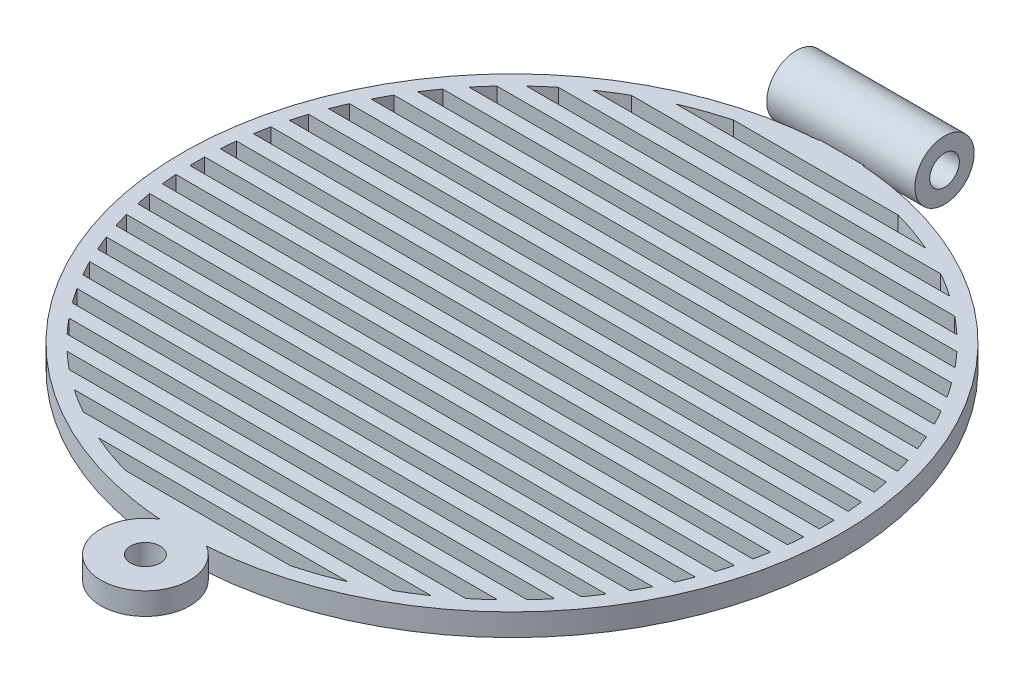
SolidWorks part; units mm, degrees
ref_plane "Front Plane" through (0, 0, 0) normal (0, 0, 1) x (1, 0, 0)
ref_plane "Top Plane" through (0, 0, 0) normal (0, 1, 0) x (1, 0, 0)
ref_plane "Right Plane" through (0, 0, 0) normal (1, 0, 0) x (0, 0, -1)
sketch "Sketch1" plane through (0, 0, 0) normal (0, 1, 0) x (1, 0, 0)
  line L1 (-1.5, 24.1894) -> (1.5, 24.1894)
  line L2 (-1.5, 24.1894) -> (-1.5, 22.1894)
  line L3 (-1.5, 22.1894) -> (1.5, 22.1894)
  line L4 (1.5, 24.1894) -> (1.5, 22.1894)
  line L5 (-1.5, 24.1894) -> (1.5, 22.1894) construction
  line L6 (-1.5, 22.1894) -> (1.5, 24.1894) construction
  circle A2 centre (0, -24.74) radius 3
  circle A3 centre (0, -24.74) radius 1
  ellipse E0 centre (0, 0) end of major axis (-21.24, 0) minor radius 21.24
  ellipse E1 centre (0, 0) end of major axis (-22.24, 0) minor radius 22.24
  point P7 (0, 23.1894)
  dimension "D1" = 1
  dimension "D2" = 21.24
  dimension "D3" = 2
  dimension "D4" = 2
  dimension "D5" = 2.5
  dimension "D6" = 3
  dimension "D7" = 0
  dimension "D8" = 2
  dimension "D9" = 21.24
  dimension "D10" = 1
  dimension "D11" = 0
extrude "Boss-Extrude1" add sketch "Sketch1" along normal blind 1.5 contours E1 A2 A3 | E1 A2 | A2 E1 L3 | L3 E1 | E1 L4 L1 L2 region at (0, 0, -23.2062) region at (0, 0, -22.2096) region at (0, 0, -21.5611) region at (0, 0, 22.0275) region at (2.5472, 0, 23.316)
sketch "Sketch2" plane through (0, 0, 0) normal (1, 0, 0) x (0, 0, -1)
  line L0 (-22.1844, 0) -> (22.1894, 0) construction
  line L2 (24.1894, 1.5) -> (24.1894, 0) construction
  circle A0 centre (24.1894, 2) radius 1
  circle A1 centre (24.1894, 2) radius 2
  dimension "D1" = 2
  dimension "D2" = 1
  dimension "D3" = 0
  dimension "2.5" = 2
extrude "Boss-Extrude2" add sketch "Sketch2" along normal blind 5 and the other way blind 5
sketch "Sketch4" plane through (5, 0, 0) normal (1, 0, 0) x (0, 0, -1)
  circle A0 centre (24.1894, 2) radius 1
extrude "Cut-Extrude1" cut sketch "Sketch4" against normal through all
sketch "Sketch5" plane through (0, 1.5, 0) normal (0, 1, 0) x (1, 0, 0)
  line L0 (-21.2341, -0.5) -> (21.2341, -0.5)
  line L1 (21.2341, 0.5) -> (-21.2341, 0.5)
  line L2 (21.2341, 2.5) -> (-21.2341, 2.5)
  line L3 (-21.2341, 1.5) -> (21.2341, 1.5)
  line L4 (21.2341, 4.5) -> (-21.2341, 4.5)
  line L5 (-21.2341, 3.5) -> (21.2341, 3.5)
  line L6 (21.2341, 6.5) -> (-21.2341, 6.5)
  line L7 (-21.2341, 5.5) -> (21.2341, 5.5)
  line L8 (21.2341, 8.5) -> (-21.2341, 8.5)
  line L9 (-21.2341, 7.5) -> (21.2341, 7.5)
  line L10 (21.2341, 10.5) -> (-21.2341, 10.5)
  line L11 (-21.2341, 9.5) -> (21.2341, 9.5)
  line L12 (21.2341, 12.5) -> (-21.2341, 12.5)
  line L13 (-21.2341, 11.5) -> (21.2341, 11.5)
  line L14 (21.2341, 14.5) -> (-21.2341, 14.5)
  line L15 (-21.2341, 13.5) -> (21.2341, 13.5)
  line L16 (21.2341, 16.5) -> (-21.2341, 16.5)
  line L17 (-21.2341, 15.5) -> (21.2341, 15.5)
  line L18 (21.2341, 18.5) -> (-21.2341, 18.5)
  line L19 (-21.2341, 17.5) -> (21.2341, 17.5)
  line L20 (21.2341, 20.5) -> (-21.2341, 20.5)
  line L21 (-21.2341, 19.5) -> (21.2341, 19.5)
  line L22 (21.2341, -1.5) -> (-21.2341, -1.5)
  line L23 (-21.2341, -2.5) -> (21.2341, -2.5)
  line L24 (21.2341, -3.5) -> (-21.2341, -3.5)
  line L25 (-21.2341, -4.5) -> (21.2341, -4.5)
  line L26 (21.2341, -5.5) -> (-21.2341, -5.5)
  line L27 (-21.2341, -6.5) -> (21.2341, -6.5)
  line L28 (21.2341, -7.5) -> (-21.2341, -7.5)
  line L29 (-21.2341, -8.5) -> (21.2341, -8.5)
  line L30 (21.2341, -9.5) -> (-21.2341, -9.5)
  line L31 (-21.2341, -10.5) -> (21.2341, -10.5)
  line L32 (21.2341, -11.5) -> (-21.2341, -11.5)
  line L33 (-21.2341, -12.5) -> (21.2341, -12.5)
  line L34 (21.2341, -13.5) -> (-21.2341, -13.5)
  line L35 (-21.2341, -14.5) -> (21.2341, -14.5)
  line L36 (21.2341, -15.5) -> (-21.2341, -15.5)
  line L37 (-21.2341, -16.5) -> (21.2341, -16.5)
  line L38 (21.2341, -17.5) -> (-21.2341, -17.5)
  line L39 (-21.2341, -18.5) -> (21.2341, -18.5)
  line L40 (21.2341, -19.5) -> (-21.2341, -19.5)
  line L41 (-21.2341, -20.5) -> (21.2341, -20.5)
  circle A0 centre (0, 0) radius 21.24 construction
  ellipse E0 centre (0, 0) end of major axis (21.24, 0) minor radius 21.24
  ellipse M10 centre (0, 0) end of major axis (0, -21.24) minor radius 21.24
  dimension "D1" = 0.5
  dimension "D2" = 0.5
  dimension "D3" = 11
  dimension "D4" = 11
extrude "Boss-Extrude3" add sketch "Sketch5" against normal up to surface (1.5 mm away) contours L22 L0 M10 | L3 L1 M10 | L5 L2 M10 | L7 L4 M10 | L9 L6 M10 | L24 L23 M10 | L26 L25 M10 | L28 L27 M10 | L30 L29 M10 | L32 L31 M10 | L34 L33 M10 | L36 L35 M10 | L38 L37 M10 | L40 L39 M10 | L41 M10 | L11 L8 M10 | L13 L10 M10 | L15 L12 M10 | L17 L14 M10 | L19 L16 M10 | L21 L18 M10 | L20 M10 region at (0, 1.5, 0.9998) region at (0, 1.5, -0.9998) region at (0, 1.5, 2.9994) region at (0, 1.5, -2.9994) region at (0, 1.5, 4.999) region at (0, 1.5, -4.999) region at (0, 1.5, 6.9985) region at (0, 1.5, -6.9985) region at (0, 1.5, 8.998) region at (0, 1.5, -8.998) region at (0, 1.5, 10.9972) region at (0, 1.5, -10.9972) region at (0, 1.5, 12.9962) region at (0, 1.5, -12.9962) region at (0, 1.5, 14.9945) region at (0, 1.5, -14.9945) region at (0, 1.5, 16.9912) region at (0, 1.5, -16.9912) region at (0, 1.5, 18.9823) region at (0, 1.5, -18.9823) region at (0, 1.5, 20.7964) region at (0, 1.5, -20.7964) up to face at (0, 0, -7.1499)
sketch "Sketch6" plane through (0, 0, 0) normal (0, -1, 0) x (1, 0, 0)
  line L0 (-0.1, 19.5) -> (-0.1, 17.0155)
  line L1 (9.9, 17.0155) -> (10.1, 17.0155)
  line L2 (7.9, -8.5) -> (7.9, -10.5)
  line L3 (0.1, 19.5) -> (0.1, 17.0155)
  line L4 (1.9, 20.5) -> (1.9, 19.5)
  line L5 (2.1, 20.5) -> (2.1, 19.5)
  line L6 (3.9, 19.5) -> (3.9, 17.0155)
  line L7 (4.1, 19.5) -> (4.1, 17.0155)
  line L8 (5.9, 20.5) -> (5.9, 19.5)
  line L9 (6.1, 20.5) -> (6.1, 19.5)
  line L10 (7.9, 19.5) -> (7.9, 17.0155)
  line L11 (8.1, 19.5) -> (8.1, 17.0155)
  line L12 (9.9, 17.0155) -> (9.9, 15.0879)
  line L13 (10.1, 17.0155) -> (10.1, 15.0879)
  line L14 (11.9, 15.0879) -> (11.9, 13.5)
  line L15 (12.1, 15.0879) -> (12.1, 13.5)
  line L16 (13.9, 17.0155) -> (13.9, 15.0879)
  line L17 (14.1, 17.0155) -> (14.1, 15.0879)
  line L18 (15.9, 15.0879) -> (15.9, 13.5)
  line L19 (16.1, 15.0879) -> (16.1, 13.5)
  line L20 (8.1, 15.0879) -> (8.1, 13.5)
  line L21 (7.9, 15.0879) -> (7.9, 13.5)
  line L24 (-1.9, 20.5) -> (-1.9, 19.5)
  line L25 (-2.1, 20.5) -> (-2.1, 19.5)
  line L26 (-3.9, 19.5) -> (-3.9, 17.0155)
  line L27 (-4.1, 19.5) -> (-4.1, 17.0155)
  line L28 (-5.9, 20.5) -> (-5.9, 19.5)
  line L29 (-6.1, 20.5) -> (-6.1, 19.5)
  line L30 (-7.9, 19.5) -> (-7.9, 16.8952)
  line L31 (-8.1, 19.5) -> (-8.1, 16.8952)
  line L32 (-9.9, 16.8952) -> (-9.9, 15.0134)
  line L33 (-10.1, 16.8952) -> (-10.1, 15.0134)
  line L34 (-11.9, 15.0134) -> (-11.9, 13.5)
  line L35 (-12.1, 15.0134) -> (-12.1, 13.5)
  line L36 (-13.9, 16.8952) -> (-13.9, 15.0134)
  line L37 (-14.1, 16.8952) -> (-14.1, 15.0134)
  line L38 (-16.1, 15.0134) -> (-15.9, 15.0134)
  line L39 (-8.1, 19.5) -> (-7.9, 19.5)
  line L40 (-17.9, 9.5) -> (-17.9, 7.5)
  line L41 (-18.1, 9.5) -> (-18.1, 7.5)
  line L42 (-19.9, 7.5) -> (-19.9, 5.5)
  line L43 (-20.1, 7.5) -> (-20.1, 5.5)
  line L44 (-20.1, -0.5) -> (-19.9, -0.5)
  line L45 (-20.1, 1.5) -> (-19.9, 1.5)
  line L46 (-20.1, 3.5) -> (-19.9, 3.5)
  line L47 (-20.1, 5.5) -> (-19.9, 5.5)
  line L48 (-20.1, 7.5) -> (-19.9, 7.5)
  line L49 (-18.1, 9.5) -> (-17.9, 9.5)
  line L50 (-14.1, 9.5) -> (-13.9, 9.5)
  line L51 (-18.1, 1.5) -> (-18.1, -0.5)
  line L52 (-7.9, 15.0134) -> (-7.9, 13.5)
  line L53 (-8.1, 15.0134) -> (-8.1, 13.5)
  line L54 (-8.1, 15.0134) -> (-7.9, 15.0134)
  line L55 (-20.1, -2.5) -> (-19.9, -2.5)
  line L56 (-20.1, -4.5) -> (-19.9, -4.5)
  line L57 (-20.1, -6.5) -> (-19.9, -6.5)
  line L58 (-18.1, -12.5) -> (-17.9, -12.5)
  line L59 (-18.1, -10.5) -> (-17.9, -10.5)
  line L60 (3.9, -8.5) -> (3.9, -10.5)
  line L61 (4.1, -8.5) -> (4.1, -10.5)
  line L62 (5.9, -8.5) -> (6.1, -8.5)
  line L64 (-12.1, -18.5) -> (-11.9, -18.5)
  line L65 (-8.1, 13.5) -> (-7.9, 13.5)
  line L66 (-0.1, 3.5) -> (0.1, 3.5)
  line L67 (-0.1, 3.5) -> (-0.1, 1.5)
  line L68 (0.1, 3.5) -> (0.1, 1.5)
  line L69 (1.9, 3.5) -> (2.1, 3.5)
  line L70 (1.9, 1.5) -> (2.1, 1.5)
  line L71 (0.1, -0.5) -> (0.1, -2.5)
  line L72 (-0.1, -0.5) -> (-0.1, -2.5)
  line L73 (-0.1, 1.5) -> (0.1, 1.5)
  line L74 (-1.9, 1.5) -> (-1.9, -0.5)
  line L75 (-2.1, 1.5) -> (-2.1, -0.5)
  line L76 (-2.1, 3.5) -> (-1.9, 3.5)
  line L77 (-2.1, 5.5) -> (-1.9, 5.5)
  line L78 (-2.1, 5.5) -> (-2.1, 3.5)
  line L79 (-1.9, 5.5) -> (-1.9, 3.5)
  line L80 (-0.1, 5.5) -> (0.1, 5.5)
  line L81 (1.9, 5.5) -> (2.1, 5.5)
  line L82 (1.9, 5.5) -> (1.9, 3.5)
  line L83 (2.1, 5.5) -> (2.1, 3.5)
  line L84 (3.9, 5.5) -> (4.1, 5.5)
  line L85 (3.9, 3.5) -> (4.1, 3.5)
  line L86 (2.1, 1.5) -> (2.1, -0.5)
  line L87 (1.9, 1.5) -> (1.9, -0.5)
  line L88 (1.9, 7.5) -> (2.1, 7.5)
  line L89 (0.1, 7.5) -> (0.1, 5.5)
  line L90 (-0.1, 7.5) -> (-0.1, 5.5)
  line L91 (-0.1, 7.5) -> (0.1, 7.5)
  line L92 (-2.1, 7.5) -> (-1.9, 7.5)
  line L93 (-2.1, 9.5) -> (-1.9, 9.5)
  line L94 (-2.1, 9.5) -> (-2.1, 7.5)
  line L95 (-1.9, 9.5) -> (-1.9, 7.5)
  line L96 (-0.1, 9.5) -> (0.1, 9.5)
  line L97 (1.9, 9.5) -> (2.1, 9.5)
  line L98 (1.9, 9.5) -> (1.9, 7.5)
  line L99 (2.1, 9.5) -> (2.1, 7.5)
  line L100 (3.9, 9.5) -> (4.1, 9.5)
  line L101 (3.9, 7.5) -> (4.1, 7.5)
  line L102 (3.9, 1.5) -> (4.1, 1.5)
  line L103 (3.9, -0.5) -> (4.1, -0.5)
  line L104 (2.1, -2.5) -> (2.1, -4.5)
  line L105 (1.9, -2.5) -> (1.9, -4.5)
  line L106 (1.9, -0.5) -> (2.1, -0.5)
  line L107 (1.9, -2.5) -> (2.1, -2.5)
  line L108 (0.1, -4.5) -> (0.1, -6.5)
  line L109 (-0.1, -4.5) -> (-0.1, -6.5)
  line L110 (-0.1, -2.5) -> (0.1, -2.5)
  line L111 (-1.9, -2.5) -> (-1.9, -4.5)
  line L112 (-2.1, -2.5) -> (-2.1, -4.5)
  line L113 (-2.1, -0.5) -> (-1.9, -0.5)
  line L114 (-2.1, 1.5) -> (-1.9, 1.5)
  line L115 (-3.9, -0.5) -> (-3.9, -2.5)
  line L116 (-4.1, -0.5) -> (-4.1, -2.5)
  line L117 (-4.1, 1.5) -> (-3.9, 1.5)
  line L118 (-4.1, 3.5) -> (-3.9, 3.5)
  line L119 (-4.1, 3.5) -> (-4.1, 1.5)
  line L120 (-3.9, 3.5) -> (-3.9, 1.5)
  line L121 (-5.9, 1.5) -> (-5.9, -0.5)
  line L122 (-6.1, 1.5) -> (-6.1, -0.5)
  line L123 (-6.1, 3.5) -> (-5.9, 3.5)
  line L124 (-6.1, 5.5) -> (-5.9, 5.5)
  line L125 (-6.1, 5.5) -> (-6.1, 3.5)
  line L126 (-5.9, 5.5) -> (-5.9, 3.5)
  line L127 (-4.1, 5.5) -> (-3.9, 5.5)
  line L128 (-3.9, 7.5) -> (-3.9, 5.5)
  line L129 (-4.1, 7.5) -> (-4.1, 5.5)
  line L130 (-4.1, 7.5) -> (-3.9, 7.5)
  line L131 (-6.1, 7.5) -> (-5.9, 7.5)
  line L132 (-6.1, 9.5) -> (-5.9, 9.5)
  line L133 (-6.1, 9.5) -> (-6.1, 7.5)
  line L134 (-5.9, 9.5) -> (-5.9, 7.5)
  line L135 (-4.1, 9.5) -> (-3.9, 9.5)
  line L136 (-2.1, 11.5) -> (-1.9, 11.5)
  line L137 (-3.9, 11.5) -> (-3.9, 9.5)
  line L138 (-4.1, 11.5) -> (-4.1, 9.5)
  line L139 (-4.1, 11.5) -> (-3.9, 11.5)
  line L140 (-6.1, 11.5) -> (-5.9, 11.5)
  line L141 (-6.1, 13.5) -> (-5.9, 13.5)
  line L142 (-6.1, 13.5) -> (-6.1, 11.5)
  line L143 (-5.9, 13.5) -> (-5.9, 11.5)
  line L144 (-4.1, 15.0879) -> (-3.9, 15.0879)
  line L145 (-4.1, 15.0879) -> (-4.1, 13.5)
  line L146 (-3.9, 15.0879) -> (-3.9, 13.5)
  line L147 (-2.1, 15.0879) -> (-1.9, 15.0879)
  line L148 (-2.1, 13.5) -> (-1.9, 13.5)
  line L149 (-4.1, 13.5) -> (-3.9, 13.5)
  line L150 (-4.1, 17.0155) -> (-3.9, 17.0155)
  line L151 (-4.1, 19.5) -> (-3.9, 19.5)
  line L152 (-2.1, 19.5) -> (-1.9, 19.5)
  line L153 (-2.1, 17.0155) -> (-1.9, 17.0155)
  line L154 (-6.1, 15.5) -> (-5.9, 15.5)
  line L155 (-6.1, 17.5) -> (-5.9, 17.5)
  line L156 (-6.1, 17.5) -> (-6.1, 15.5)
  line L157 (-5.9, 17.5) -> (-5.9, 15.5)
  line L158 (-6.1, 19.5) -> (-5.9, 19.5)
  line L159 (-6.1, 20.5) -> (-5.9, 20.5)
  line L160 (-2.1, 20.5) -> (-1.9, 20.5)
  line L161 (-2.1, 17.0155) -> (-2.1, 15.0879)
  line L162 (-1.9, 17.0155) -> (-1.9, 15.0879)
  line L163 (-0.1, 17.0155) -> (0.1, 17.0155)
  line L164 (-0.1, 15.0879) -> (0.1, 15.0879)
  line L165 (-1.9, 13.5) -> (-1.9, 11.5)
  line L166 (-2.1, 13.5) -> (-2.1, 11.5)
  line L167 (-0.1, 11.5) -> (0.1, 11.5)
  line L168 (-0.1, 13.5) -> (0.1, 13.5)
  line L169 (-0.1, 11.5) -> (-0.1, 9.5)
  line L170 (0.1, 11.5) -> (0.1, 9.5)
  line L171 (1.9, 11.5) -> (2.1, 11.5)
  line L172 (3.9, 11.5) -> (4.1, 11.5)
  line L173 (3.9, 13.5) -> (4.1, 13.5)
  line L174 (2.1, 13.5) -> (2.1, 11.5)
  line L175 (1.9, 13.5) -> (1.9, 11.5)
  line L176 (1.9, 15.0879) -> (2.1, 15.0879)
  line L177 (1.9, 13.5) -> (2.1, 13.5)
  line L178 (0.1, 15.0879) -> (0.1, 13.5)
  line L179 (-0.1, 15.0879) -> (-0.1, 13.5)
  line L180 (-0.1, 19.5) -> (0.1, 19.5)
  line L181 (1.9, 19.5) -> (2.1, 19.5)
  line L182 (1.9, 20.5) -> (2.1, 20.5)
  line L183 (1.9, 17.0155) -> (2.1, 17.0155)
  line L184 (3.9, 15.0879) -> (4.1, 15.0879)
  line L185 (3.9, 17.0155) -> (4.1, 17.0155)
  line L186 (2.1, 17.0155) -> (2.1, 15.0879)
  line L187 (1.9, 17.0155) -> (1.9, 15.0879)
  line L188 (3.9, 19.5) -> (4.1, 19.5)
  line L189 (5.9, 20.5) -> (6.1, 20.5)
  line L190 (5.9, 19.5) -> (6.1, 19.5)
  line L191 (5.9, 17.0155) -> (6.1, 17.0155)
  line L192 (4.1, 15.0879) -> (4.1, 13.5)
  line L193 (3.9, 15.0879) -> (3.9, 13.5)
  line L194 (3.9, 11.5) -> (3.9, 9.5)
  line L195 (4.1, 11.5) -> (4.1, 9.5)
  line L196 (5.9, 13.5) -> (6.1, 13.5)
  line L197 (5.9, 15.0879) -> (6.1, 15.0879)
  line L198 (13.9, 17.0155) -> (14.1, 17.0155)
  line L199 (7.9, 19.5) -> (8.1, 19.5)
  line L200 (6.1, 17.0155) -> (6.1, 15.0879)
  line L201 (5.9, 17.0155) -> (5.9, 15.0879)
  line L202 (5.9, 13.5) -> (5.9, 11.5)
  line L203 (6.1, 13.5) -> (6.1, 11.5)
  line L204 (7.9, 15.0879) -> (8.1, 15.0879)
  line L205 (7.9, 17.0155) -> (8.1, 17.0155)
  line L206 (15.9, 15.0879) -> (16.1, 15.0879)
  line L209 (13.9, 15.0879) -> (14.1, 15.0879)
  line L210 (15.9, 7.5) -> (15.9, 5.5)
  line L211 (17.9, 19.5) -> (17.9, 17.5) [skipped]
  line L212 (18.1, 19.5) -> (18.1, 17.5) [skipped]
  line L213 (16.1, 7.5) -> (16.1, 5.5)
  line L214 (11.9, 15.0879) -> (12.1, 15.0879)
  line L215 (19.9, 7.5) -> (19.9, 5.5)
  line L216 (20.1, 7.5) -> (20.1, 5.5)
  line L217 (9.9, 15.0879) -> (10.1, 15.0879)
  line L218 (9.9, 13.5) -> (9.9, 11.5)
  line L219 (10.1, 13.5) -> (10.1, 11.5)
  line L220 (13.9, 13.5) -> (13.9, 11.5)
  line L221 (14.1, 13.5) -> (14.1, 11.5)
  line L222 (7.9, 11.5) -> (7.9, 9.5)
  line L223 (8.1, 11.5) -> (8.1, 9.5)
  line L224 (11.9, 11.5) -> (11.9, 9.5)
  line L225 (12.1, 11.5) -> (12.1, 9.5)
  line L226 (15.9, 11.5) -> (15.9, 9.5)
  line L227 (16.1, 11.5) -> (16.1, 9.5)
  line L228 (5.9, 9.5) -> (5.9, 7.5)
  line L229 (6.1, 9.5) -> (6.1, 7.5)
  line L230 (9.9, 9.5) -> (9.9, 7.5)
  line L231 (10.1, 9.5) -> (10.1, 7.5)
  line L232 (13.9, 9.5) -> (13.9, 7.5)
  line L233 (14.1, 9.5) -> (14.1, 7.5)
  line L234 (17.9, 9.5) -> (17.9, 7.5)
  line L235 (18.1, 9.5) -> (18.1, 7.5)
  line L236 (3.9, 7.5) -> (3.9, 5.5)
  line L237 (4.1, 7.5) -> (4.1, 5.5)
  line L238 (7.9, 7.5) -> (7.9, 5.5)
  line L239 (8.1, 7.5) -> (8.1, 5.5)
  line L240 (11.9, 7.5) -> (11.9, 5.5)
  line L241 (12.1, 7.5) -> (12.1, 5.5)
  line L242 (15.9, 13.5) -> (16.1, 13.5)
  line L245 (17.9, 9.5) -> (18.1, 9.5)
  line L246 (15.9, 9.5) -> (16.1, 9.5)
  line L247 (15.9, 11.5) -> (16.1, 11.5)
  line L248 (13.9, 13.5) -> (14.1, 13.5)
  line L249 (13.9, 11.5) -> (14.1, 11.5)
  line L250 (13.9, 9.5) -> (14.1, 9.5)
  line L251 (11.9, 9.5) -> (12.1, 9.5)
  line L252 (11.9, 11.5) -> (12.1, 11.5)
  line L253 (11.9, 13.5) -> (12.1, 13.5)
  line L254 (9.9, 13.5) -> (10.1, 13.5)
  line L255 (9.9, 11.5) -> (10.1, 11.5)
  line L256 (9.9, 9.5) -> (10.1, 9.5)
  line L257 (7.9, 9.5) -> (8.1, 9.5)
  line L258 (7.9, 11.5) -> (8.1, 11.5)
  line L259 (7.9, 13.5) -> (8.1, 13.5)
  line L260 (5.9, 11.5) -> (6.1, 11.5)
  line L261 (5.9, 9.5) -> (6.1, 9.5)
  line L264 (19.9, 11.5) -> (19.9, 9.5) [skipped]
  line L265 (20.1, 11.5) -> (20.1, 9.5) [skipped]
  line L266 (19.9, 7.5) -> (20.1, 7.5)
  line L267 (18.1, 5.5) -> (18.1, 3.5)
  line L268 (17.9, 5.5) -> (17.9, 3.5)
  line L269 (17.9, 7.5) -> (18.1, 7.5)
  line L270 (15.9, 7.5) -> (16.1, 7.5)
  line L271 (13.9, 5.5) -> (13.9, 3.5)
  line L272 (14.1, 5.5) -> (14.1, 3.5)
  line L273 (10.1, 5.5) -> (10.1, 3.5)
  line L274 (9.9, 5.5) -> (9.9, 3.5)
  line L275 (6.1, 5.5) -> (6.1, 3.5)
  line L276 (5.9, 5.5) -> (5.9, 3.5)
  line L277 (4.1, 3.5) -> (4.1, 1.5)
  line L278 (3.9, 3.5) -> (3.9, 1.5)
  line L279 (7.9, 3.5) -> (7.9, 1.5)
  line L280 (8.1, 3.5) -> (8.1, 1.5)
  line L281 (11.9, 3.5) -> (11.9, 1.5)
  line L282 (12.1, 3.5) -> (12.1, 1.5)
  line L283 (15.9, 3.5) -> (15.9, 1.5)
  line L284 (16.1, 3.5) -> (16.1, 1.5)
  line L285 (19.9, 3.5) -> (19.9, 1.5)
  line L286 (20.1, 3.5) -> (20.1, 1.5)
  line L287 (18.1, 1.5) -> (18.1, -0.5)
  line L288 (17.9, 1.5) -> (17.9, -0.5)
  line L289 (14.1, 1.5) -> (14.1, -0.5)
  line L290 (13.9, 1.5) -> (13.9, -0.5)
  line L291 (10.1, 1.5) -> (10.1, -0.5)
  line L292 (9.9, 1.5) -> (9.9, -0.5)
  line L293 (6.1, 1.5) -> (6.1, -0.5)
  line L294 (5.9, 1.5) -> (5.9, -0.5)
  line L295 (4.1, -0.5) -> (4.1, -2.5)
  line L296 (3.9, -0.5) -> (3.9, -2.5)
  line L297 (7.9, -0.5) -> (7.9, -2.5)
  line L298 (8.1, -0.5) -> (8.1, -2.5)
  line L299 (11.9, -0.5) -> (11.9, -2.5)
  line L300 (12.1, -0.5) -> (12.1, -2.5)
  line L301 (15.9, -0.5) -> (15.9, -2.5)
  line L302 (16.1, -0.5) -> (16.1, -2.5)
  line L303 (19.9, -0.5) -> (19.9, -2.5)
  line L304 (20.1, -0.5) -> (20.1, -2.5)
  line L305 (18.1, -2.5) -> (18.1, -4.5)
  line L306 (17.9, -2.5) -> (17.9, -4.5)
  line L307 (14.1, -2.5) -> (14.1, -4.5)
  line L308 (13.9, -2.5) -> (13.9, -4.5)
  line L309 (10.1, -2.5) -> (10.1, -4.5)
  line L310 (9.9, -2.5) -> (9.9, -4.5)
  line L311 (6.1, -2.5) -> (6.1, -4.5)
  line L312 (5.9, -2.5) -> (5.9, -4.5)
  line L313 (5.9, 7.5) -> (6.1, 7.5)
  line L314 (7.9, 7.5) -> (8.1, 7.5)
  line L315 (9.9, 7.5) -> (10.1, 7.5)
  line L316 (11.9, 7.5) -> (12.1, 7.5)
  line L317 (13.9, 7.5) -> (14.1, 7.5)
  line L318 (13.9, 5.5) -> (14.1, 5.5)
  line L319 (11.9, 5.5) -> (12.1, 5.5)
  line L320 (9.9, 5.5) -> (10.1, 5.5)
  line L321 (7.9, 5.5) -> (8.1, 5.5)
  line L322 (5.9, 5.5) -> (6.1, 5.5)
  line L323 (5.9, 3.5) -> (6.1, 3.5)
  line L324 (7.9, 3.5) -> (8.1, 3.5)
  line L325 (9.9, 3.5) -> (10.1, 3.5)
  line L326 (9.9, 1.5) -> (10.1, 1.5)
  line L327 (7.9, 1.5) -> (8.1, 1.5)
  line L328 (5.9, 1.5) -> (6.1, 1.5)
  line L329 (11.9, 3.5) -> (12.1, 3.5)
  line L330 (11.9, 1.5) -> (12.1, 1.5)
  line L331 (13.9, 1.5) -> (14.1, 1.5)
  line L332 (13.9, 3.5) -> (14.1, 3.5)
  line L333 (15.9, 5.5) -> (16.1, 5.5)
  line L334 (15.9, 3.5) -> (16.1, 3.5)
  line L335 (15.9, 1.5) -> (16.1, 1.5)
  line L336 (17.9, 1.5) -> (18.1, 1.5)
  line L337 (17.9, 3.5) -> (18.1, 3.5)
  line L338 (17.9, 5.5) -> (18.1, 5.5)
  line L339 (19.9, 5.5) -> (20.1, 5.5)
  line L340 (19.9, 3.5) -> (20.1, 3.5)
  line L341 (19.9, 1.5) -> (20.1, 1.5)
  line L342 (-8.1, 11.5) -> (-8.1, 9.5)
  line L343 (-6.1, -8.5) -> (-5.9, -8.5)
  line L344 (-14.1, 16.8952) -> (-13.9, 16.8952)
  line L345 (-15.9, 15.0134) -> (-15.9, 13.5)
  line L346 (-16.1, 15.0134) -> (-16.1, 13.5)
  line L347 (-6.1, -10.5) -> (-6.1, -12.5)
  line L348 (-16.1, 19.5) -> (-16.1, 17.5) [skipped]
  line L349 (-15.9, 19.5) -> (-15.9, 17.5) [skipped]
  line L350 (-5.9, -10.5) -> (-5.9, -12.5)
  line L351 (-21.2341, 19.5) -> (-19.9, 19.5) [skipped]
  line L352 (-20.1, 17.5) -> (-19.9, 17.5) [skipped]
  line L353 (-21.2341, 15.5) -> (-19.9, 15.5) [skipped]
  line L354 (-7.9, 11.5) -> (-7.9, 9.5)
  line L355 (-7.9, 7.5) -> (-7.9, 5.5)
  line L356 (-8.1, 7.5) -> (-8.1, 5.5)
  line L357 (-8.1, 7.5) -> (-7.9, 7.5)
  line L358 (-8.1, 5.5) -> (-7.9, 5.5)
  line L359 (-8.1, 3.5) -> (-7.9, 3.5)
  line L360 (-8.1, 3.5) -> (-8.1, 1.5)
  line L361 (-7.9, 3.5) -> (-7.9, 1.5)
  line L362 (-6.1, 1.5) -> (-5.9, 1.5)
  line L363 (-7.9, -0.5) -> (-7.9, -2.5)
  line L364 (-8.1, -0.5) -> (-8.1, -2.5)
  line L365 (-8.1, -0.5) -> (-7.9, -0.5)
  line L366 (-8.1, -2.5) -> (-7.9, -2.5)
  line L367 (-8.1, -4.5) -> (-8.1, -6.5)
  line L368 (-7.9, -4.5) -> (-7.9, -6.5)
  line L369 (-6.1, -4.5) -> (-5.9, -4.5)
  line L370 (-6.1, -6.5) -> (-5.9, -6.5)
  line L371 (-7.9, -8.5) -> (-7.9, -10.5)
  line L372 (-8.1, -8.5) -> (-8.1, -10.5)
  line L373 (-8.1, -8.5) -> (-7.9, -8.5)
  line L374 (-8.1, -10.5) -> (-7.9, -10.5)
  line L375 (-8.1, -12.5) -> (-8.1, -14.5)
  line L376 (-7.9, -12.5) -> (-7.9, -14.5)
  line L377 (-6.1, -12.5) -> (-5.9, -12.5)
  line L378 (-6.1, -14.5) -> (-5.9, -14.5)
  line L379 (-6.1, -0.5) -> (-5.9, -0.5)
  line L380 (-6.1, -2.5) -> (-5.9, -2.5)
  line L381 (-6.1, -2.5) -> (-6.1, -4.5)
  line L382 (-5.9, -2.5) -> (-5.9, -4.5)
  line L383 (-4.1, -2.5) -> (-3.9, -2.5)
  line L384 (-4.1, -4.5) -> (-3.9, -4.5)
  line L385 (-5.9, -6.5) -> (-5.9, -8.5)
  line L386 (-6.1, -6.5) -> (-6.1, -8.5)
  line L387 (-4.1, -10.5) -> (-3.9, -10.5)
  line L388 (-4.1, -12.5) -> (-3.9, -12.5)
  line L389 (-5.9, -14.5) -> (-5.9, -16.5)
  line L390 (-6.1, -14.5) -> (-6.1, -16.5)
  line L391 (-3.9, -4.5) -> (-3.9, -6.5)
  line L392 (-4.1, -4.5) -> (-4.1, -6.5)
  line L393 (-4.1, -6.5) -> (-3.9, -6.5)
  line L394 (-4.1, -8.5) -> (-4.1, -10.5)
  line L395 (-3.9, -8.5) -> (-3.9, -10.5)
  line L396 (-2.1, -6.5) -> (-1.9, -6.5)
  line L397 (-2.1, -4.5) -> (-1.9, -4.5)
  line L398 (-2.1, -6.5) -> (-2.1, -8.5)
  line L399 (-1.9, -6.5) -> (-1.9, -8.5)
  line L400 (-0.1, -6.5) -> (0.1, -6.5)
  line L401 (-0.1, -8.5) -> (0.1, -8.5)
  line L402 (-1.9, -10.5) -> (-1.9, -12.5)
  line L403 (-2.1, -10.5) -> (-2.1, -12.5)
  line L404 (-2.1, -10.5) -> (-1.9, -10.5)
  line L405 (-2.1, -12.5) -> (-1.9, -12.5)
  line L406 (-2.1, -14.5) -> (-2.1, -16.5)
  line L407 (-1.9, -14.5) -> (-1.9, -16.5)
  line L408 (-3.9, -12.5) -> (-3.9, -14.5)
  line L409 (-4.1, -12.5) -> (-4.1, -14.5)
  line L410 (-2.1, -8.5) -> (-1.9, -8.5)
  line L411 (-4.1, -8.5) -> (-3.9, -8.5)
  line L412 (-0.1, -4.5) -> (0.1, -4.5)
  line L413 (1.9, -4.5) -> (2.1, -4.5)
  line L414 (1.9, -6.5) -> (2.1, -6.5)
  line L415 (0.1, -8.5) -> (0.1, -10.5)
  line L416 (-0.1, -8.5) -> (-0.1, -10.5)
  line L417 (-0.1, -10.5) -> (0.1, -10.5)
  line L418 (-0.1, -12.5) -> (-0.1, -14.5)
  line L419 (0.1, -12.5) -> (0.1, -14.5)
  line L420 (1.9, -12.5) -> (2.1, -12.5)
  line L421 (1.9, -10.5) -> (2.1, -10.5)
  line L422 (1.9, -8.5) -> (2.1, -8.5)
  line L423 (1.9, -6.5) -> (1.9, -8.5)
  line L424 (2.1, -6.5) -> (2.1, -8.5)
  line L425 (3.9, -4.5) -> (3.9, -6.5)
  line L426 (4.1, -4.5) -> (4.1, -6.5)
  line L427 (7.9, -4.5) -> (7.9, -6.5)
  line L428 (8.1, -4.5) -> (8.1, -6.5)
  line L429 (11.9, -4.5) -> (11.9, -6.5)
  line L430 (12.1, -4.5) -> (12.1, -6.5)
  line L431 (15.9, -4.5) -> (15.9, -6.5)
  line L432 (16.1, -4.5) -> (16.1, -6.5)
  line L433 (19.9, -4.5) -> (19.9, -6.5)
  line L434 (20.1, -4.5) -> (20.1, -6.5)
  line L435 (18.1, -6.5) -> (18.1, -8.5)
  line L436 (17.9, -6.5) -> (17.9, -8.5)
  line L437 (14.1, -6.5) -> (14.1, -8.5)
  line L438 (13.9, -6.5) -> (13.9, -8.5)
  line L439 (10.1, -6.5) -> (10.1, -8.5)
  line L440 (9.9, -6.5) -> (9.9, -8.5)
  line L441 (6.1, -6.5) -> (6.1, -8.5)
  line L442 (5.9, -6.5) -> (5.9, -8.5)
  line L443 (-12.1, 15.0134) -> (-11.9, 15.0134)
  line L444 (-10.1, 15.0134) -> (-9.9, 15.0134)
  line L445 (-10.1, 13.5) -> (-9.9, 13.5)
  line L446 (-11.9, 11.5) -> (-11.9, 9.5)
  line L447 (-12.1, 11.5) -> (-12.1, 9.5)
  line L448 (-12.1, 13.5) -> (-11.9, 13.5)
  line L449 (-10.1, 13.5) -> (-10.1, 11.5)
  line L450 (-9.9, 13.5) -> (-9.9, 11.5)
  line L451 (-13.9, 13.5) -> (-13.9, 11.5)
  line L452 (-14.1, 13.5) -> (-14.1, 11.5)
  line L453 (-14.1, 15.0134) -> (-13.9, 15.0134)
  line L454 (-10.1, 16.8952) -> (-9.9, 16.8952)
  line L455 (-16.1, 13.5) -> (-15.9, 13.5)
  line L456 (-16.1, 11.5) -> (-16.1, 9.5)
  line L457 (-15.9, 11.5) -> (-15.9, 9.5)
  line L458 (-14.1, 13.5) -> (-13.9, 13.5)
  line L459 (-14.1, 11.5) -> (-13.9, 11.5)
  line L460 (-14.1, 9.5) -> (-14.1, 7.5)
  line L461 (-13.9, 9.5) -> (-13.9, 7.5)
  line L462 (-12.1, 11.5) -> (-11.9, 11.5)
  line L463 (-10.1, 11.5) -> (-9.9, 11.5)
  line L464 (-10.1, 9.5) -> (-9.9, 9.5)
  line L465 (-11.9, 7.5) -> (-11.9, 5.5)
  line L466 (-12.1, 7.5) -> (-12.1, 5.5)
  line L467 (-12.1, 7.5) -> (-11.9, 7.5)
  line L468 (-12.1, 5.5) -> (-11.9, 5.5)
  line L469 (-12.1, 3.5) -> (-12.1, 1.5)
  line L470 (-11.9, 3.5) -> (-11.9, 1.5)
  line L471 (-10.1, 5.5) -> (-9.9, 5.5)
  line L472 (-10.1, 7.5) -> (-9.9, 7.5)
  line L473 (-10.1, 9.5) -> (-10.1, 7.5)
  line L474 (-9.9, 9.5) -> (-9.9, 7.5)
  line L475 (-9.9, 5.5) -> (-9.9, 3.5)
  line L476 (-10.1, 5.5) -> (-10.1, 3.5)
  line L477 (-8.1, 9.5) -> (-7.9, 9.5)
  line L478 (-8.1, 11.5) -> (-7.9, 11.5)
  line L479 (-21.2341, 13.5) -> (-17.9, 13.5) [skipped]
  line L480 (-16.1, 11.5) -> (-15.9, 11.5)
  line L481 (-21.2341, 11.5) -> (-19.9, 11.5) [skipped]
  line L482 (-14.1, 7.5) -> (-13.9, 7.5)
  line L483 (-14.1, 5.5) -> (-13.9, 5.5)
  line L484 (-14.1, 3.5) -> (-13.9, 3.5)
  line L485 (-14.1, 1.5) -> (-13.9, 1.5)
  line L486 (-15.9, 7.5) -> (-15.9, 5.5)
  line L487 (-16.1, 7.5) -> (-16.1, 5.5)
  line L488 (-18.1, 7.5) -> (-17.9, 7.5)
  line L489 (-18.1, 5.5) -> (-18.1, 3.5)
  line L490 (-17.9, 5.5) -> (-17.9, 3.5)
  line L491 (-14.1, 5.5) -> (-14.1, 3.5)
  line L492 (-13.9, 5.5) -> (-13.9, 3.5)
  line L493 (-15.9, 3.5) -> (-15.9, 1.5)
  line L494 (-16.1, 3.5) -> (-16.1, 1.5)
  line L495 (-19.9, 3.5) -> (-19.9, 1.5)
  line L496 (-20.1, 3.5) -> (-20.1, 1.5)
  line L497 (-17.9, 1.5) -> (-17.9, -0.5)
  line L498 (-10.1, 1.5) -> (-10.1, -0.5)
  line L499 (-9.9, 1.5) -> (-9.9, -0.5)
  line L500 (-13.9, 1.5) -> (-13.9, -0.5)
  line L501 (-14.1, 1.5) -> (-14.1, -0.5)
  line L502 (-19.9, -0.5) -> (-19.9, -2.5)
  line L503 (-20.1, -0.5) -> (-20.1, -2.5)
  line L504 (-16.1, -0.5) -> (-16.1, -2.5)
  line L505 (-15.9, -0.5) -> (-15.9, -2.5)
  line L506 (-12.1, -0.5) -> (-12.1, -2.5)
  line L507 (-11.9, -0.5) -> (-11.9, -2.5)
  line L508 (-9.9, -2.5) -> (-9.9, -4.5)
  line L509 (-10.1, -2.5) -> (-10.1, -4.5)
  line L510 (-14.1, -2.5) -> (-14.1, -4.5)
  line L511 (-13.9, -2.5) -> (-13.9, -4.5)
  line L512 (-17.9, -2.5) -> (-17.9, -4.5)
  line L513 (-18.1, -2.5) -> (-18.1, -4.5)
  line L514 (-19.9, -4.5) -> (-19.9, -6.5)
  line L515 (-20.1, -4.5) -> (-20.1, -6.5)
  line L516 (-16.1, -4.5) -> (-16.1, -6.5)
  line L517 (-15.9, -4.5) -> (-15.9, -6.5)
  line L518 (-12.1, -4.5) -> (-12.1, -6.5)
  line L519 (-11.9, -4.5) -> (-11.9, -6.5)
  line L520 (-9.9, -6.5) -> (-9.9, -8.5)
  line L521 (-10.1, -6.5) -> (-10.1, -8.5)
  line L522 (-14.1, -6.5) -> (-14.1, -8.5)
  line L523 (-13.9, -6.5) -> (-13.9, -8.5)
  line L524 (-17.9, -6.5) -> (-17.9, -8.5)
  line L525 (-18.1, -6.5) -> (-18.1, -8.5)
  line L526 (5.9, -10.5) -> (6.1, -10.5)
  line L527 (4.1, -12.5) -> (4.1, -14.5)
  line L528 (-18.1, -6.5) -> (-17.9, -6.5)
  line L529 (-18.1, -4.5) -> (-17.9, -4.5)
  line L530 (-18.1, -2.5) -> (-17.9, -2.5)
  line L531 (-16.1, -0.5) -> (-15.9, -0.5)
  line L532 (-16.1, -2.5) -> (-15.9, -2.5)
  line L533 (-16.1, -4.5) -> (-15.9, -4.5)
  line L534 (-14.1, -4.5) -> (-13.9, -4.5)
  line L535 (-14.1, -2.5) -> (-13.9, -2.5)
  line L536 (-14.1, -0.5) -> (-13.9, -0.5)
  line L537 (-12.1, -0.5) -> (-11.9, -0.5)
  line L538 (-12.1, -2.5) -> (-11.9, -2.5)
  line L539 (-10.1, -2.5) -> (-9.9, -2.5)
  line L540 (-10.1, -0.5) -> (-9.9, -0.5)
  line L541 (-10.1, -4.5) -> (-9.9, -4.5)
  line L542 (-12.1, -4.5) -> (-11.9, -4.5)
  line L543 (-12.1, -6.5) -> (-11.9, -6.5)
  line L544 (-12.1, -8.5) -> (-11.9, -8.5)
  line L545 (-14.1, -6.5) -> (-13.9, -6.5)
  line L546 (-14.1, -8.5) -> (-13.9, -8.5)
  line L547 (-11.9, -8.5) -> (-11.9, -10.5)
  line L548 (-12.1, -8.5) -> (-12.1, -10.5)
  line L549 (-15.9, -8.5) -> (-15.9, -10.5)
  line L550 (-16.1, -8.5) -> (-16.1, -10.5)
  line L551 (-18.1, -8.5) -> (-17.9, -8.5)
  line L552 (-17.9, -10.5) -> (-17.9, -12.5)
  line L553 (-18.1, -10.5) -> (-18.1, -12.5)
  line L554 (-14.1, -10.5) -> (-14.1, -12.5)
  line L555 (-13.9, -10.5) -> (-13.9, -12.5)
  line L556 (-10.1, -10.5) -> (-10.1, -12.5)
  line L557 (-9.9, -10.5) -> (-9.9, -12.5)
  line L558 (1.9, -10.5) -> (1.9, -12.5)
  line L559 (2.1, -10.5) -> (2.1, -12.5)
  line L560 (-18.1, 5.5) -> (-17.9, 5.5)
  line L561 (-16.1, 7.5) -> (-15.9, 7.5)
  line L562 (-16.1, 9.5) -> (-15.9, 9.5)
  line L563 (-12.1, 9.5) -> (-11.9, 9.5)
  line L564 (-16.1, 5.5) -> (-15.9, 5.5)
  line L565 (-16.1, 3.5) -> (-15.9, 3.5)
  line L566 (-18.1, 3.5) -> (-17.9, 3.5)
  line L567 (-18.1, 1.5) -> (-17.9, 1.5)
  line L568 (-16.1, 1.5) -> (-15.9, 1.5)
  line L569 (-12.1, 3.5) -> (-11.9, 3.5)
  line L570 (-12.1, 1.5) -> (-11.9, 1.5)
  line L571 (-10.1, 1.5) -> (-9.9, 1.5)
  line L572 (-10.1, 3.5) -> (-9.9, 3.5)
  line L573 (-8.1, 1.5) -> (-7.9, 1.5)
  line L574 (-2.1, -2.5) -> (-1.9, -2.5)
  line L575 (3.9, -2.5) -> (4.1, -2.5)
  line L576 (3.9, -4.5) -> (4.1, -4.5)
  line L577 (5.9, -4.5) -> (6.1, -4.5)
  line L578 (5.9, -2.5) -> (6.1, -2.5)
  line L579 (5.9, -0.5) -> (6.1, -0.5)
  line L580 (7.9, -0.5) -> (8.1, -0.5)
  line L581 (7.9, -2.5) -> (8.1, -2.5)
  line L582 (7.9, -4.5) -> (8.1, -4.5)
  line L583 (9.9, -0.5) -> (10.1, -0.5)
  line L584 (9.9, -2.5) -> (10.1, -2.5)
  line L585 (9.9, -4.5) -> (10.1, -4.5)
  line L586 (11.9, -0.5) -> (12.1, -0.5)
  line L587 (11.9, -2.5) -> (12.1, -2.5)
  line L588 (11.9, -4.5) -> (12.1, -4.5)
  line L589 (13.9, -0.5) -> (14.1, -0.5)
  line L590 (13.9, -2.5) -> (14.1, -2.5)
  line L591 (13.9, -4.5) -> (14.1, -4.5)
  line L592 (19.9, -4.5) -> (20.1, -4.5)
  line L593 (-20.1, -8.5) -> (-19.9, -8.5) [skipped]
  line L594 (-16.1, -6.5) -> (-15.9, -6.5)
  line L595 (-14.1, -16.5) -> (-13.9, -16.5)
  line L596 (3.9, -12.5) -> (3.9, -14.5)
  line L597 (3.9, -12.5) -> (4.1, -12.5)
  line L598 (-20.1, -14.5) -> (-19.9, -14.5) [skipped]
  line L599 (-21.2341, -12.5) -> (-19.9, -12.5) [skipped]
  line L600 (-21.2341, -16.5) -> (-19.9, -16.5) [skipped]
  line L601 (-21.2341, -20.5) -> (-19.9, -20.5) [skipped]
  line L602 (-20.1, -18.5) -> (-19.9, -18.5) [skipped]
  line L603 (3.9, -14.5) -> (4.1, -14.5)
  line L604 (3.9, -16.5) -> (3.9, -18.5)
  line L605 (4.1, -16.5) -> (4.1, -18.5)
  line L606 (5.9, -14.5) -> (6.1, -14.5)
  line L607 (2.1, -14.5) -> (2.1, -16.5)
  line L608 (1.9, -14.5) -> (1.9, -16.5)
  line L609 (1.9, -14.5) -> (2.1, -14.5)
  line L610 (1.9, -16.5) -> (2.1, -16.5)
  line L611 (1.9, -18.5) -> (1.9, -20.5)
  line L612 (2.1, -18.5) -> (2.1, -20.5)
  line L613 (3.9, -16.5) -> (4.1, -16.5)
  line L614 (5.9, -16.5) -> (6.1, -16.5)
  line L615 (5.9, -18.5) -> (6.1, -18.5)
  line L616 (3.9, -18.5) -> (4.1, -18.5)
  line L617 (5.9, -14.5) -> (5.9, -16.5)
  line L618 (6.1, -14.5) -> (6.1, -16.5)
  line L619 (7.9, -14.5) -> (8.1, -14.5)
  line L620 (7.9, -16.5) -> (8.1, -16.5)
  line L621 (6.1, -18.5) -> (6.1, -20.5)
  line L622 (5.9, -18.5) -> (5.9, -20.5)
  line L623 (-16.1, -10.5) -> (-15.9, -10.5)
  line L624 (-16.1, -12.5) -> (-15.9, -12.5)
  line L625 (-16.1, -8.5) -> (-15.9, -8.5)
  line L626 (-16.1, -12.5) -> (-16.1, -14.5)
  line L627 (-16.1, -14.5) -> (-15.9, -14.5)
  line L628 (-15.9, -12.5) -> (-15.9, -14.5)
  line L629 (-14.1, -12.5) -> (-13.9, -12.5)
  line L630 (-14.1, -14.5) -> (-13.9, -14.5)
  line L631 (-13.9, -14.5) -> (-13.9, -16.5)
  line L632 (-14.1, -14.5) -> (-14.1, -16.5)
  line L633 (-12.1, -16.5) -> (-11.9, -16.5)
  line L634 (-12.1, -14.5) -> (-11.9, -14.5)
  line L635 (-12.1, -10.5) -> (-11.9, -10.5)
  line L636 (-12.1, -12.5) -> (-12.1, -14.5)
  line L637 (-11.9, -12.5) -> (-11.9, -14.5)
  line L638 (-10.1, -12.5) -> (-9.9, -12.5)
  line L639 (-10.1, -14.5) -> (-9.9, -14.5)
  line L640 (-11.9, -16.5) -> (-11.9, -18.5)
  line L641 (-12.1, -16.5) -> (-12.1, -18.5)
  line L642 (-8.1, -16.5) -> (-8.1, -18.5)
  line L643 (-7.9, -16.5) -> (-7.9, -18.5)
  line L644 (-3.9, -16.5) -> (-3.9, -18.5)
  line L645 (-4.1, -16.5) -> (-4.1, -18.5)
  line L646 (-2.1, -18.5) -> (-2.1, -20.5)
  line L647 (-1.9, -18.5) -> (-1.9, -20.5)
  line L648 (-6.1, -18.5) -> (-6.1, -20.5)
  line L649 (-5.9, -18.5) -> (-5.9, -20.5)
  line L652 (-10.1, -16.5) -> (-9.9, -16.5)
  line L653 (-8.1, -14.5) -> (-7.9, -14.5)
  line L654 (-8.1, -16.5) -> (-7.9, -16.5)
  line L655 (-8.1, -12.5) -> (-7.9, -12.5)
  line L656 (-12.1, -12.5) -> (-11.9, -12.5)
  line L657 (-4.1, -14.5) -> (-3.9, -14.5)
  line L658 (-4.1, -16.5) -> (-3.9, -16.5)
  line L659 (-6.1, -16.5) -> (-5.9, -16.5)
  line L660 (-6.1, -10.5) -> (-5.9, -10.5)
  line L661 (-10.1, -8.5) -> (-9.9, -8.5)
  line L662 (-10.1, -10.5) -> (-9.9, -10.5)
  line L663 (-8.1, -4.5) -> (-7.9, -4.5)
  line L664 (-8.1, -6.5) -> (-7.9, -6.5)
  line L665 (-10.1, -6.5) -> (-9.9, -6.5)
  line L667 (-6.1, -20.5) -> (-5.9, -20.5)
  line L668 (-8.1, -18.5) -> (-7.9, -18.5)
  line L669 (-6.1, -18.5) -> (-5.9, -18.5)
  line L670 (-4.1, -18.5) -> (-3.9, -18.5)
  line L671 (-2.1, -20.5) -> (-1.9, -20.5)
  line L672 (1.9, -20.5) -> (2.1, -20.5)
  line L673 (-0.1, -18.5) -> (0.1, -18.5)
  line L674 (0.1, -16.5) -> (0.1, -18.5)
  line L675 (-0.1, -16.5) -> (-0.1, -18.5)
  line L676 (-0.1, -16.5) -> (0.1, -16.5)
  line L677 (-2.1, -16.5) -> (-1.9, -16.5)
  line L678 (-2.1, -14.5) -> (-1.9, -14.5)
  line L679 (-0.1, -14.5) -> (0.1, -14.5)
  line L680 (-0.1, -12.5) -> (0.1, -12.5)
  line L681 (3.9, -8.5) -> (4.1, -8.5)
  line L682 (3.9, -10.5) -> (4.1, -10.5)
  line L683 (1.9, -18.5) -> (2.1, -18.5)
  line L684 (-2.1, -18.5) -> (-1.9, -18.5)
  line L685 (5.9, -20.5) -> (6.1, -20.5)
  line L686 (7.9, -18.5) -> (8.1, -18.5)
  line L691 (11.9, -18.5) -> (12.1, -18.5)
  line L692 (7.9, -6.5) -> (8.1, -6.5)
  line L693 (5.9, -6.5) -> (6.1, -6.5)
  line L694 (3.9, -6.5) -> (4.1, -6.5)
  line L695 (8.1, -8.5) -> (8.1, -10.5)
  line L696 (9.9, -8.5) -> (10.1, -8.5)
  line L697 (9.9, -10.5) -> (10.1, -10.5)
  line L698 (8.1, -12.5) -> (8.1, -14.5)
  line L699 (7.9, -12.5) -> (7.9, -14.5)
  line L700 (7.9, -12.5) -> (8.1, -12.5)
  line L701 (7.9, -16.5) -> (7.9, -18.5)
  line L702 (8.1, -16.5) -> (8.1, -18.5)
  line L703 (12.1, -8.5) -> (12.1, -10.5)
  line L704 (11.9, -8.5) -> (11.9, -10.5)
  line L705 (11.9, -8.5) -> (12.1, -8.5)
  line L706 (11.9, -10.5) -> (12.1, -10.5)
  line L707 (11.9, -12.5) -> (11.9, -14.5)
  line L708 (12.1, -12.5) -> (12.1, -14.5)
  line L709 (13.9, -12.5) -> (14.1, -12.5)
  line L710 (13.9, -14.5) -> (14.1, -14.5)
  line L711 (12.1, -16.5) -> (12.1, -18.5)
  line L712 (11.9, -16.5) -> (11.9, -18.5)
  line L713 (13.9, -10.5) -> (13.9, -12.5)
  line L714 (14.1, -10.5) -> (14.1, -12.5)
  line L715 (19.9, -6.5) -> (20.1, -6.5)
  line L716 (17.9, -6.5) -> (18.1, -6.5)
  line L717 (15.9, -2.5) -> (16.1, -2.5)
  line L718 (17.9, -2.5) -> (18.1, -2.5)
  line L719 (19.9, -2.5) -> (20.1, -2.5)
  line L720 (17.9, -4.5) -> (18.1, -4.5)
  line L721 (15.9, -4.5) -> (16.1, -4.5)
  line L722 (15.9, -6.5) -> (16.1, -6.5)
  line L723 (15.9, -8.5) -> (15.9, -10.5)
  line L724 (16.1, -8.5) -> (16.1, -10.5)
  line L725 (7.9, -8.5) -> (8.1, -8.5)
  line L726 (7.9, -10.5) -> (8.1, -10.5)
  line L727 (9.9, -6.5) -> (10.1, -6.5)
  line L728 (9.9, -10.5) -> (9.9, -12.5)
  line L729 (10.1, -10.5) -> (10.1, -12.5)
  line L730 (6.1, -10.5) -> (6.1, -12.5)
  line L731 (5.9, -10.5) -> (5.9, -12.5)
  line L732 (-8.1, 16.8952) -> (-7.9, 16.8952)
  line L733 (15.9, -8.5) -> (16.1, -8.5)
  line L734 (15.9, -10.5) -> (16.1, -10.5)
  line L735 (15.9, -12.5) -> (16.1, -12.5)
  line L736 (15.9, -14.5) -> (16.1, -14.5)
  line L737 (17.9, -8.5) -> (18.1, -8.5)
  line L738 (17.9, -10.5) -> (17.9, -12.5)
  line L739 (18.1, -10.5) -> (18.1, -12.5)
  line L740 (13.9, -8.5) -> (14.1, -8.5)
  line L741 (13.9, -10.5) -> (14.1, -10.5)
  line L742 (-9.9, -14.5) -> (-9.9, -16.5)
  line L743 (-10.1, -14.5) -> (-10.1, -16.5)
  line L744 (9.9, -14.5) -> (9.9, -16.5)
  line L745 (10.1, -14.5) -> (10.1, -16.5)
  line L746 (11.9, -12.5) -> (12.1, -12.5)
  line L747 (11.9, -14.5) -> (12.1, -14.5)
  line L748 (9.9, -14.5) -> (10.1, -14.5)
  line L749 (9.9, -12.5) -> (10.1, -12.5)
  line L750 (5.9, -12.5) -> (6.1, -12.5)
  line L751 (9.9, -16.5) -> (10.1, -16.5)
  line L752 (11.9, -16.5) -> (12.1, -16.5)
  line L753 (13.9, -16.5) -> (14.1, -16.5)
  line L754 (14.1, -14.5) -> (14.1, -16.5)
  line L755 (13.9, -14.5) -> (13.9, -16.5)
  line L756 (17.9, -10.5) -> (18.1, -10.5)
  line L757 (16.1, -12.5) -> (16.1, -14.5)
  line L758 (15.9, -12.5) -> (15.9, -14.5)
  line L759 (17.9, -12.5) -> (18.1, -12.5)
  line L760 (-18.1, -0.5) -> (-17.9, -0.5)
  line L761 (-0.1, -0.5) -> (0.1, -0.5)
  line L762 (-4.1, -0.5) -> (-3.9, -0.5)
  line L763 (15.9, -0.5) -> (16.1, -0.5)
  line L764 (17.9, -0.5) -> (18.1, -0.5)
  line L765 (19.9, -0.5) -> (20.1, -0.5)
  line L766 (-14.1, -10.5) -> (-13.9, -10.5)
  line L767 (11.9, -6.5) -> (12.1, -6.5)
  line L768 (13.9, -6.5) -> (14.1, -6.5)
  dimension "D1" = 0.1
  dimension "D2" = 0.1
  dimension "D3" = 11
  dimension "D4" = 11
  dimension "D5" = 11
  dimension "D6" = 11
extrude "Boss-Extrude4" add sketch "Sketch6" against normal blind 0.5
